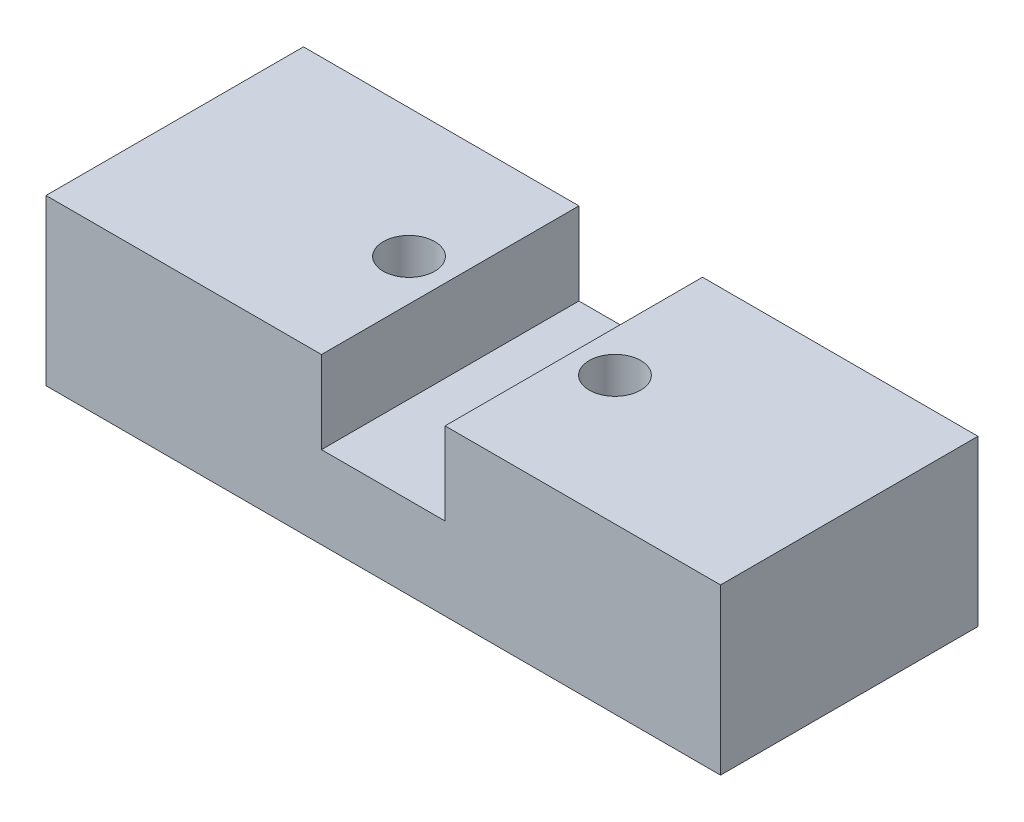
SolidWorks part; units mm, degrees
ref_plane "Płaszczyzna przednia" through (0, 0, 0) normal (0, 0, 1) x (1, 0, 0)
ref_plane "Płaszczyzna górna" through (0, 0, 0) normal (0, 1, 0) x (1, 0, 0)
ref_plane "Płaszczyzna prawa" through (0, 0, 0) normal (1, 0, 0) x (0, 0, -1)
sketch "Sketch1" plane through (0, 0, 0) normal (0, 0, 1) x (1, 0, 0)
  line L0 (26.75, 16) -> (26.75, 8)
  line L1 (0, 0) -> (65.5, 0)
  line L2 (0, 0) -> (0, 16)
  line L3 (0, 16) -> (26.75, 16)
  line L4 (65.5, 0) -> (65.5, 16)
  line L5 (26.75, 8) -> (38.75, 8)
  line L6 (38.75, 8) -> (38.75, 16)
  line L7 (38.75, 16) -> (65.5, 16)
  dimension "D1" = 65.5
  dimension "D2" = 16
  dimension "D3" = 26.75
  dimension "D4" = 26.75
  dimension "D5" = 8
extrude "Boss-Extrude1" add sketch "Sketch1" along normal blind 25
hole_wizard "Ø5.0mm Dowel Hole1" positions "Sketch2" profile "Sketch4" hole size "Ø5.0" standard "ANSI Metric" end condition through all
sketch "Sketch2" plane through (0, 16, 0) normal (0, 1, 0) x (1, 0, 0)
  line L0 (26.75, -25) -> (26.75, 0) construction
  line L1 (38.75, -25) -> (38.75, 0) construction
  line L2 (65.5, -25) -> (38.75, -25) construction
  point P0 (22.75, -12.5)
  point P2 (42.75, -12.5)
  point P9 (0, 0)
  dimension "D1" = 4
  dimension "D2" = 4
  dimension "D3" = 12.5
sketch "Sketch4" plane through (22.75, 16, 12.5) normal (1, 0, 0) x (0, 0, 1)
  line L0 (0, 0) -> (0, 16)
  line L1 (0, 16) -> (2.5, 16)
  line L2 (2.5, 16) -> (2.5, 0)
  line L5 (2.5, 0) -> (0, 0)
  line L11 (0, -6.35) -> (0, 107.95) construction
  dimension "Thru Hole Dia." = 5
  dimension "Thru Hole Depth" = 16
